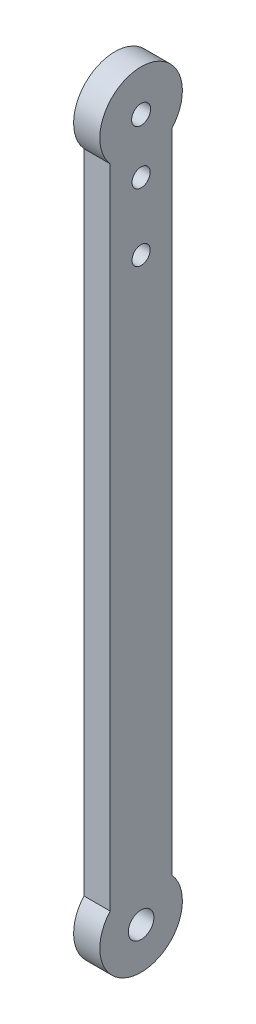
SolidWorks part; units mm, degrees
ref_plane "Front Plane" through (0, 0, 0) normal (0, 0, 1) x (1, 0, 0)
ref_plane "Top Plane" through (0, 0, 0) normal (0, 1, 0) x (1, 0, 0)
ref_plane "Right Plane" through (0, 0, 0) normal (1, 0, 0) x (0, 0, -1)
sketch "Sketch1" plane through (0, 0, 0) normal (1, 0, 0) x (0, 0, -1)
  line L0 (0, 0) -> (-3.75, -3.3072) construction
  line L2 (3.75, -3.3072) -> (3.75, -81.6928)
  line L3 (3.75, -81.6928) -> (-3.75, -81.6928) construction
  line L4 (-3.75, -3.3072) -> (-3.75, -81.6928)
  line L5 (3.75, -3.3072) -> (-3.75, -3.3072) construction
  line L6 (0, 0) -> (3.75, -3.3072) construction
  arc A1 (3.75, -3.3072) -> (-3.75, -3.3072) centre (0, 0) ccw
  arc A2 (-3.75, -81.6928) -> (3.75, -81.6928) centre (0, -85) ccw
  circle A3 centre (0, -85) radius 1.55
  circle A24 centre (0, -14.75) radius 1.1
  circle A264 centre (0, 0) radius 1.15
  circle A265 centre (0, -6.6) radius 1.1
  dimension "D1" = 2.3
  dimension "D2" = 10
  dimension "D4" = 10
  dimension "D6" = 3.1
  dimension "D7" = 2.2
  dimension "D3" = 7.5
  dimension "D5" = 85
  dimension "D8" = 8.15
  dimension "D9" = 6.6
extrude "Boss-Extrude3" add sketch "Sketch1" along normal blind 3.175
